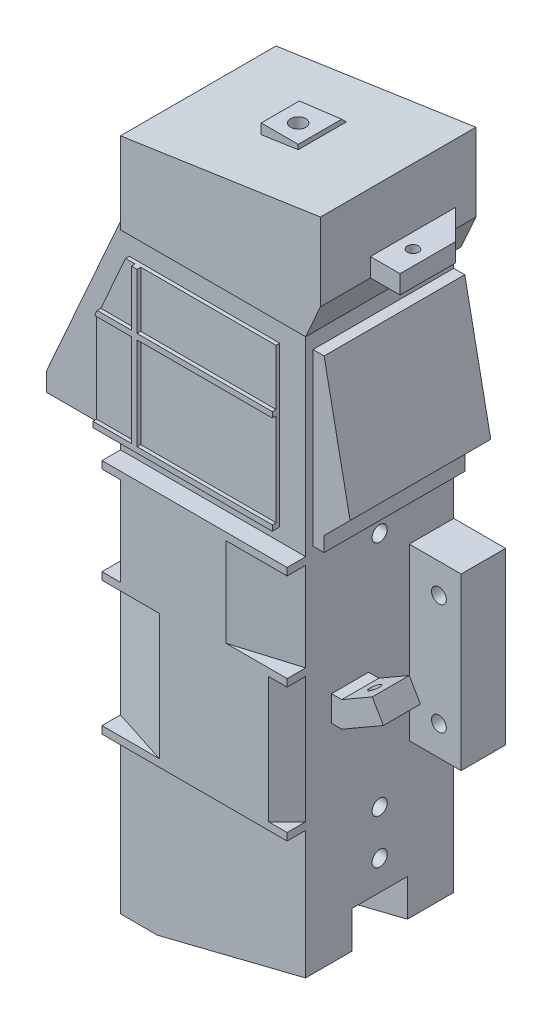
SolidWorks part; units mm, degrees
ref_plane "Front" through (0, 0, 0) normal (0, 0, 1) x (1, 0, 0)
ref_plane "Top" through (0, 0, 0) normal (0, 1, 0) x (1, 0, 0)
ref_plane "Right" through (0, 0, 0) normal (1, 0, 0) x (0, 0, -1)
sketch "Sketch1" plane through (0, 0, 0) normal (0, 0, 1) x (1, 0, 0)
  line L0 (-25, 81) -> (-45, 36)
  line L1 (-25, -81) -> (25, -81)
  line L2 (-25, -81) -> (-25, 81)
  line L3 (-25, 81) -> (25, 81)
  line L4 (25, -81) -> (25, 81)
  line L5 (-25, -81) -> (25, 81) construction
  line L6 (-25, 81) -> (25, -81) construction
  line L7 (-45, 36) -> (-45, 31)
  line L8 (-45, 31) -> (-25, 31)
  line L9 (-15, -81) -> (25, -71)
  point P0 (0, 0)
  dimension "D1" = 162
  dimension "D2" = 50
  dimension "D3" = 20
  dimension "D4" = 5
  dimension "D5" = 112
  dimension "D6" = 10
  dimension "D7" = 10
extrude "Boss-Extrude1" add sketch "Sketch1" along normal blind 40 contours L1 L9 L4 L3 L2 | L7 L8 L2 L0 region at (-32.2727, 47.8182, 0) region at (-0.2954, 1.9662, 0)
sketch "Sketch2" plane through (0, 0, 40) normal (0, 0, 1) x (1, 0, 0)
  line L0 (-23, 81) -> (-23, 103)
  line L1 (-25, 81) -> (25, 81) construction
  line L2 (-23, 103) -> (31, 111)
  line L3 (31, 111) -> (31, 90)
  line L4 (31, 90) -> (27, 81)
  line L5 (27, 81) -> (25, 81)
  line L6 (-23, 81) -> (25, 81)
  dimension "D1" = 2
  dimension "D2" = 2
  dimension "D3" = 22
  dimension "D4" = 30
  dimension "D5" = 6
  dimension "D6" = 9
extrude "Boss-Extrude2" add sketch "Sketch2" against normal blind 40 and the other way blind 2 contours L2 L3 L4 L5 L6 L0
sketch "Sketch3" plane through (0, 0, 40) normal (0, 0, 1) x (1, 0, 0)
  line L0 (-25, 20.3294) -> (-19.7915, 25.5379)
  line L1 (-25, 5.5379) -> (25, 5.5379)
  line L2 (-25, 5.5379) -> (-25, -34.4621)
  line L3 (-25, -34.4621) -> (25, -34.4621)
  line L4 (25, 5.5379) -> (25, -34.4621)
  line L5 (-25, 5.5379) -> (25, -34.4621) construction
  line L6 (-25, -34.4621) -> (25, 5.5379) construction
  line L7 (25, 5.5379) -> (-25, 5.5379)
  line L8 (25, 5.5379) -> (25, 25.5379)
  line L9 (25, 25.5379) -> (-25, 25.5379)
  line L10 (-25, 5.5379) -> (-25, 25.5379)
  line L11 (25, 5.5379) -> (-25, 25.5379) construction
  line L12 (25, 25.5379) -> (-25, 5.5379) construction
  line L13 (-25, -81) -> (-25, 31) construction
  line L14 (-25, -81) -> (-25, 31)
  line L15 (25, -71) -> (25, 81) construction
  point P4 (0, -14.4621)
  point P9 (0, 15.5379)
  line M12 (25, -71) -> (25, 81)
  line M18 (-25, 31) -> (-25, -81)
  dimension "D1" = 20
  dimension "D2" = 40
extrude "Boss-Extrude3" add sketch "Sketch3" along normal blind 5 contours L3 L1 M18 M12 | L9 L0 L1 M12 M18 region at (0.3199, 15.4243, 40) region at (0, -14.4621, 40)
sketch "Sketch4" plane through (0, -34.4621, 0) normal (0, -1, 0) x (1, 0, 0)
  line L0 (25, 40) -> (20, 45)
  line L1 (-25, 45) -> (25, 45) construction
  line L2 (-25, 40) -> (-9.5194, 45)
  line L3 (-25, 40) -> (-25, 45)
  line L4 (-25, 45) -> (25, 45)
  line L5 (25, 45) -> (25, 40)
  line M2 (25, 40) -> (25, 45)
  line M3 (25, 45) -> (-25, 45)
  line M4 (-25, 45) -> (-25, 40)
extrude "Cut-Extrude1" cut sketch "Sketch4" against normal blind 34 contours L2 M4 M3 | L0 M2 M3 region at (-19.8398, -34.4621, 43.3333) region at (23.3333, -34.4621, 43.3333)
sketch "Sketch5" plane through (0, 25.5379, 0) normal (0, 1, 0) x (1, 0, 0)
  line L0 (25, -40) -> (8.4624, -45)
  line L1 (25, -45) -> (-19.7915, -45) construction
  line L2 (8.4624, -45) -> (25, -45)
  line L3 (25, -45) -> (25, -40)
  line L4 (-25, -45) -> (-25, -40) construction
  line L5 (-25, -45) -> (-19.7915, -45) construction
  line L6 (-25, -45) -> (-25, -40)
  line L7 (-25, -45) -> (-19.7915, -45)
  line L8 (-25, -40) -> (-20, -45)
  line M3 (-19.7915, -45) -> (25, -45)
  line M4 (25, -45) -> (25, -40)
extrude "Cut-Extrude2" cut sketch "Sketch5" against normal blind 24 contours L8 L6 L7 | L0 M4 M3 region at (19.4875, 25.5379, 43.3333) region at (-23.3333, 25.5379, 43.3333)
sketch "Sketch6" plane through (0, 0, 40) normal (0, 0, 1) x (1, 0, 0)
  line L0 (-45, 31) -> (-25, 31) construction
  line L32 (-30.4309, 56.4693) -> (-30.4309, 31)
  line L33 (18, 74) -> (-23, 74)
  line L34 (18, 25.5379) -> (18, 74)
  line L35 (18, 74) -> (-23, 74)
  line L36 (18, 25.5379) -> (18, 74)
  line L37 (-20.4309, 78.9693) -> (-40.4309, 33.9693)
  line L38 (-20.4309, 78.9693) -> (-40.4309, 33.9693)
  line L39 (18, 31) -> (-42, 31)
  line L40 (18, 31) -> (18, 32.5)
  line L41 (18, 32.5) -> (-42, 32.5)
  line L42 (-42, 31) -> (-42, 32.5)
  line L43 (18, 31) -> (-42, 32.5) construction
  line L44 (18, 32.5) -> (-42, 31) construction
  line L45 (18, 57.4898) -> (-42, 57.4898)
  line L46 (18, 57.4898) -> (18, 58.9898)
  line L47 (18, 58.9898) -> (-42, 58.9898)
  line L48 (-42, 57.4898) -> (-42, 58.9898)
  line L49 (18, 57.4898) -> (-42, 58.9898) construction
  line L50 (18, 58.9898) -> (-42, 57.4898) construction
  line L51 (-20.0294, 31) -> (-18.5294, 31)
  line L52 (-20.0294, 31) -> (-20.0294, 77.3626)
  line L53 (-20.0294, 77.3626) -> (-18.5294, 77.3626)
  line L54 (-18.5294, 31) -> (-18.5294, 77.3626)
  line L55 (-20.0294, 31) -> (-18.5294, 77.3626) construction
  line L56 (-20.0294, 77.3626) -> (-18.5294, 31) construction
  line L57 (-30.4309, 31) -> (18, 31)
  point P6 (-12, 31.75)
  point P11 (-12, 58.2398)
  point P12 (-19.2794, 54.1813)
  point P22 (-40, 58.9898)
  point P23 (-21.7835, 27.6229)
  point P24 (-18.5294, 31)
  line M17 (-45, 31) -> (-25, 31)
  dimension "D3" = 1.5
  dimension "D4" = 60
  dimension "D5" = 1.5
  dimension "D6" = 60
  dimension "D7" = 1.5
  dimension "D1" = 7
  dimension "D2" = 5
extrude "Boss-Extrude4" add sketch "Sketch6" along normal blind 1 contours L41 L52 L45 L38 L32 | L39 L52 L41 L32 M17 | L39 L54 L41 L52 | L41 L54 L45 L52 | L54 L39 L36 L41 | L54 L41 L36 L45 | L45 L52 L47 L38 | L47 L54 L35 L52 | L47 L52 L35 L38 | L54 L47 L36 L35 | L45 L54 L47 L52 | L54 L45 L36 L47 region at (-25.2257, 44.984, 40) region at (-25.2302, 31.75, 40) region at (-24.8387, 58.2311, 40) region at (-19.2794, 44.9949, 40) region at (-19.2794, 31.75, 40) region at (-23.3142, 65.0914, 40) region at (-19.2794, 58.2398, 40) region at (-0.2647, 44.9949, 40) region at (-0.2647, 31.75, 40) region at (-19.2794, 66.4949, 40) region at (-0.2647, 58.2398, 40) region at (-0.2647, 66.4949, 40)
extrude "Boss-Extrude6" add sketch "Sketch6<4>" along normal blind 2 contours L39 L52 L41 L32 M17 | L41 L54 L45 L52 | L39 L54 L41 L52 | L54 L39 L36 L41 | L47 L54 L35 L52 | L45 L52 L47 L38 | L45 L54 L47 L52 | L54 L45 L36 L47 region at (-25.2302, 31.75, 40) region at (-24.8387, 58.2311, 40) region at (-19.2794, 44.9949, 40) region at (-19.2794, 31.75, 40) region at (-19.2794, 58.2398, 40) region at (-0.2647, 31.75, 40) region at (-19.2794, 66.4949, 40) region at (-0.2647, 58.2398, 40)
sketch "Sketch6<4>" plane through (0, 0, 40) normal (0, 0, 1) x (1, 0, 0) same geometry as "Sketch6"
sketch "Sketch8" plane through (-45, 0, 0) normal (-1, 0, 0) x (0, 0, 1)
  line L0 (40, 36) -> (0, 36) construction
  line L1 (12.5, 36) -> (27.5, 36)
  line L2 (12.5, 36) -> (12.5, 86)
  line L3 (12.5, 86) -> (27.5, 86)
  line L4 (27.5, 36) -> (27.5, 86)
  line L5 (12.5, 36) -> (27.5, 86) construction
  line L6 (12.5, 86) -> (27.5, 36) construction
  point P4 (20, 61)
  dimension "D1" = 50
  dimension "D2" = 15
  dimension "D3" = 20
extrude "Cut-Extrude3" cut sketch "Sketch8" against normal blind 20
sketch "Sketch9" plane through (0, 0, 40) normal (0, 0, 1) x (1, 0, 0)
  line L1 (-25, -34.4621) -> (25, -34.4621)
  line L2 (-25, -34.4621) -> (-25, -36.4621)
  line L3 (-25, -36.4621) -> (25, -36.4621)
  line L4 (25, -34.4621) -> (25, -36.4621)
  line L5 (-25, -34.4621) -> (25, -36.4621) construction
  line L6 (-25, -36.4621) -> (25, -34.4621) construction
  line L7 (25, -71) -> (25, -34.4621) construction
  line L9 (25, 25.5379) -> (-25, 25.5379)
  line L10 (25, 25.5379) -> (25, 27.5379)
  line L11 (25, 27.5379) -> (-25, 27.5379)
  line L12 (-25, 25.5379) -> (-25, 27.5379)
  line L13 (25, 25.5379) -> (-25, 27.5379) construction
  line L14 (25, 27.5379) -> (-25, 25.5379) construction
  point P4 (0, -35.4621)
  point P13 (0, 26.5379)
  dimension "D1" = 2
  dimension "D2" = 50
  dimension "D3" = 2
  dimension "D4" = 50
extrude "Boss-Extrude7" add sketch "Sketch9" along normal up to surface (5 mm away) up to face at (-1.685, 0.9065, 45)
sketch "Sketch10" plane through (0, -81, 0) normal (0, -1, 0) x (1, 0, 0)
  line L0 (-25, 40) -> (-25, 0) construction
  line L1 (-20, 27.5) -> (30, 27.5)
  line L2 (-20, 27.5) -> (-20, 12.5)
  line L3 (-20, 12.5) -> (30, 12.5)
  line L4 (30, 27.5) -> (30, 12.5)
  line L5 (-20, 27.5) -> (30, 12.5) construction
  line L6 (-20, 12.5) -> (30, 27.5) construction
  line L7 (-15, 40) -> (25, 40) construction
  point P4 (5, 20)
  dimension "D1" = 15
  dimension "D2" = 50
  dimension "D3" = 5
  dimension "D4" = 20
extrude "Cut-Extrude4" cut sketch "Sketch10" against normal blind 20
sketch "Sketch11" plane through (0, 36, 0) normal (0, 1, 0) x (1, 0, 0)
  line L0 (-45, -20) -> (-25, -20) construction
  line L1 (-45, -12.5) -> (-45, -27.5) construction
  line L2 (-25, -27.5) -> (-25, -12.5) construction
  circle A0 centre (-35, -20) radius 1.6
  dimension "D1" = 3.2
extrude "Cut-Extrude5" cut sketch "Sketch11" against normal up to next
sketch "Sketch12" plane through (-20, 0, 0) normal (1, 0, 0) x (0, 0, -1)
  line L0 (-20, -81) -> (-20, -61) construction
  line L1 (-27.5, -81) -> (-12.5, -81) construction
  line L2 (-12.5, -61) -> (-27.5, -61) construction
  circle A0 centre (-20, -71) radius 1.6
  dimension "D1" = 3.2
extrude "Cut-Extrude6" cut sketch "Sketch12" against normal up to next
ref_plane "Plane1" through (0, 0, 38) normal (0, 0, 1) x (1, 0, 0)
sketch "Sketch13" plane through (0, 0, 38) normal (0, 0, 1) x (1, 0, 0)
  line L0 (25, 75) -> (28, 75)
  line L1 (25, 27.5379) -> (25, 81) construction
  line L2 (28, 75) -> (35, 40)
  line L3 (35, 40) -> (28, 33)
  line L4 (28, 33) -> (28, 29)
  line L5 (28, 29) -> (25, 29)
  line L6 (25, 29) -> (25, 75)
  line L7 (-23, 81) -> (25, 81) construction
  dimension "D1" = 3
  dimension "D2" = 3
  dimension "D3" = 10
  dimension "D4" = 4
  dimension "D5" = 7
  dimension "D6" = 6
  dimension "D7" = 46
extrude "Boss-Extrude8" add sketch "Sketch13" against normal up to surface (38 mm away) up to face at (-6.6923, 37.9231, 0)
ref_plane "Plane3" through (0, 16.5, 0) normal (0, -1, 0) x (-1, 0, 0)
sketch "Sketch15" plane through (0, 16.5, 0) normal (0, -1, 0) x (-1, 0, 0)
  line L0 (-25, 0) -> (-39, 0)
  line L1 (-35, 0) -> (-28, 0) construction
  line L2 (-39, 0) -> (-39, -12)
  line L3 (-39, -12) -> (-25, -12)
  line L7 (-25, -12) -> (-25, 0)
  dimension "D1" = 14
  dimension "D2" = 12
extrude "Boss-Extrude9" add sketch "Sketch15" along normal blind 46
ref_plane "Plane4" through (0, 109, 0) normal (0, 1, 0) x (1, 0, 0)
sketch "Sketch16" plane through (0, 109, 0) normal (0, 1, 0) x (1, 0, 0)
  line L0 (-23, -21) -> (31, -21) construction
  line L1 (-23, -42) -> (-23, 0) construction
  line L2 (31, -42) -> (31, 0) construction
  line L4 (-1, -26) -> (9, -26)
  line L5 (-1, -26) -> (-1, -16)
  line L6 (-1, -16) -> (9, -16)
  line L7 (9, -26) -> (9, -16)
  line L8 (-1, -26) -> (9, -16) construction
  line L9 (-1, -16) -> (9, -26) construction
  point P6 (4, -21)
  dimension "D1" = 10
extrude "Boss-Extrude10" add sketch "Sketch16" against normal up to next
chamfer "Chamfer1" distance 3 angle 45 1 edges at (4, 107, 16)
sketch "Sketch17" plane through (0, 109, 0) normal (0, 1, 0) x (1, 0, 0)
  line L0 (4, -26) -> (4, -21) construction
  line L1 (-1, -26) -> (9, -26) construction
  circle A0 centre (4, -21) radius 2.05
  dimension "D2" = 4.1
  dimension "D1" = 5
extrude "Cut-Extrude7" cut sketch "Sketch17" against normal blind 6
sketch "Sketch18" plane through (31, 0, 0) normal (1, 0, 0) x (0, 0, -1)
  line L0 (-42, 92.5) -> (0, 92.5) construction
  line L1 (-28.5, 95) -> (-13.5, 95)
  line L2 (-28.5, 95) -> (-28.5, 90)
  line L3 (-28.5, 90) -> (-13.5, 90)
  line L4 (-13.5, 95) -> (-13.5, 90)
  line L5 (-28.5, 95) -> (-13.5, 90) construction
  line L6 (-28.5, 90) -> (-13.5, 95) construction
  line L7 (-42, 111) -> (-42, 90) construction
  line L8 (0, 111) -> (0, 90) construction
  line L9 (-42, 90) -> (0, 90) construction
  point P0 (-21, 92.5)
  dimension "D1" = 5
  dimension "D2" = 15
  dimension "D3" = 0
extrude "Boss-Extrude11" add sketch "Sketch18" along normal blind 8
chamfer "Chamfer2" distance 8 angle 45 1 edges at (31, 92.5, 13.5)
sketch "Sketch19" plane through (0, 95, 0) normal (0, 1, 0) x (1, 0, 0)
  line L0 (39, -21) -> (31, -21) construction
  line L1 (39, -13.5) -> (39, -28.5) construction
  line L2 (31, -42) -> (31, 0) construction
  circle A0 centre (35, -21) radius 1.5
  dimension "D1" = 3
extrude "Cut-Extrude8" cut sketch "Sketch19" against normal up to next
sketch "Sketch20" plane through (0, 0, 0) normal (0, 0, -1) x (-1, 0, 0)
  line L0 (-8.3163, 93.2726) -> (0.3163, 90.7274) construction
  line L2 (23, 103) -> (-31, 111) construction
  line L4 (-4, 107) -> (-4, 92) construction
  line L5 (1, 106.2593) -> (-9, 107.7407) construction
  circle A0 centre (-8.3163, 93.2726) radius 2.05
  circle A1 centre (0.3163, 90.7274) radius 2.05
  dimension "D1" = 8
  dimension "D2" = 4.1
  dimension "D3" = 4.1
  dimension "D4" = 9
  dimension "D5" = 15
extrude "Cut-Extrude9" cut sketch "Sketch20" against normal blind 8
sketch "Sketch21" plane through (0, 0, 12) normal (0, 0, 1) x (1, 0, 0)
  line L0 (39, -29.5) -> (39, 16.5) construction
  line L1 (39, -29.5) -> (25, -29.5) construction
  line L2 (39, 16.5) -> (25, 16.5) construction
  circle A0 centre (33, 8.5) radius 2
  circle A1 centre (33, -21.5) radius 2
  dimension "D1" = 4
  dimension "D2" = 4
  dimension "D5" = 8
  dimension "D3" = 6
  dimension "D4" = 8
extrude "Cut-Extrude10" cut sketch "Sketch21" against normal up to next
ref_plane "Plane5" through (0, 0, 33) normal (0, 0, 1) x (1, 0, 0)
sketch "Sketch24" plane through (0, 0, 33) normal (0, 0, 1) x (1, 0, 0)
  line L0 (25, -7.9906) -> (27.7728, -7.9906)
  line L1 (25, 1.5379) -> (25, 25.5379) construction
  line L2 (27.7728, -7.9906) -> (36, -3.2406)
  line L3 (36, -3.2406) -> (39, -8.4368)
  line L4 (39, -8.4368) -> (27.7728, -14.9188)
  line L5 (27.7728, -14.9188) -> (25, -14.9188)
  line L6 (25, -0.4621) -> (25, 1.5379) construction
  line L7 (39, -29.5) -> (39, 16.5) construction
  line L8 (25, -7.9906) -> (25, -14.9188)
  line L9 (25, -13.0556) -> (102.2316, 31.5341) construction
  line L10 (33, -21.5) -> (83.12, -21.5) construction
  line L11 (83.12, -21.5) -> (83.12, 20.5)
  line L12 (37.5, -5.8387) -> (32.4875, -8.7327) construction
  dimension "D2" = 6
  dimension "D3" = 9.5
  dimension "D4" = 60
  dimension "D5" = 50.12
  dimension "D6" = 42
extrude "Boss-Extrude13" add sketch "Sketch24" against normal blind 10 contours L0 L8 L5 L4 L3 L2 region at (31.28, -9.3909, 33)
sketch "Sketch25" plane through (13.4032, -23.2151, 0) normal (0.5, -0.866, 0) x (0.866, 0.5, 0)
  line L0 (29.5566, 33) -> (19.5566, 23) construction
  line L1 (29.5566, 23) -> (16.5925, 23) construction
  circle A0 centre (24.5566, 28) radius 1.5
  dimension "D2" = 3
  dimension "D1" = 10
extrude "Cut-Extrude12" cut sketch "Sketch25" against normal up to next
sketch "Sketch26" plane through (25, 0, 0) normal (1, 0, 0) x (0, 0, -1)
  line L0 (-12.5, -61) -> (-27.5, -61) construction
  line L1 (-40, -71) -> (-40, -36.4621) construction
  line L3 (0, 29) -> (-38, 29) construction
  circle A0 centre (-20, -41) radius 2.05
  circle A1 centre (-20, -53) radius 2.05
  circle A3 centre (-20, 23) radius 2.05
  point P10 (0, 0)
  point P11 (0, 0)
  dimension "D1" = 4.1
  dimension "D2" = 4.1
  dimension "D4" = 8
  dimension "D6" = 4.1
  dimension "D3" = 12
  dimension "D5" = 20
  dimension "D7" = 6
extrude "Cut-Extrude13" cut sketch "Sketch26" against normal blind 6
